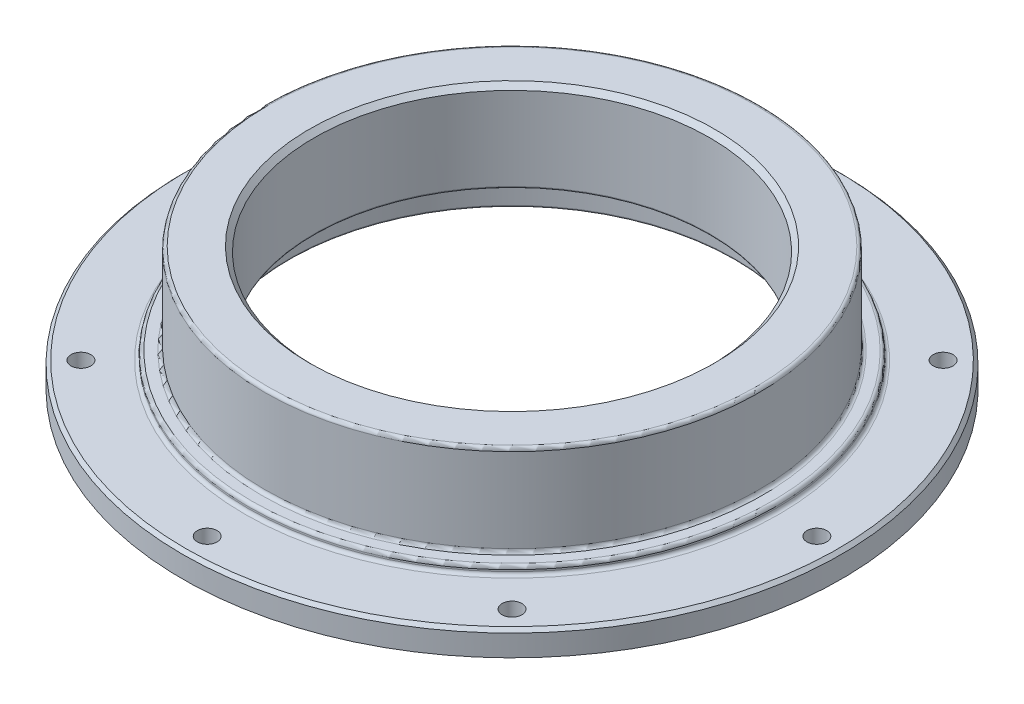
SolidWorks part; units mm, degrees
ref_plane "Front Plane" through (0, 0, 0) normal (0, 0, 1) x (1, 0, 0)
ref_plane "Top Plane" through (0, 0, 0) normal (0, 1, 0) x (1, 0, 0)
ref_plane "Right Plane" through (0, 0, 0) normal (1, 0, 0) x (0, 0, -1)
sketch "Sketch1" plane through (0, 0, 0) normal (0, 0, 1) x (1, 0, 0)
  line L0 (200, 0) -> (200, 15)
  line L1 (200, 15) -> (160, 15)
  line L2 (160, 15) -> (160, 20)
  line L3 (160, 20) -> (150, 20)
  line L4 (150, 20) -> (150, 75)
  line L5 (150, 75) -> (120, 75)
  line L6 (120, 75) -> (120, 0)
  line L7 (120, 0) -> (200, 0)
  line L8 (0, 0) -> (0, 134.8777) construction
  line L9 (120, 20.5) -> (135, 20.5)
  line L10 (135, 20.5) -> (135, 0)
  dimension "D1" = 200
  dimension "D2" = 75
  dimension "D3" = 5
  dimension "D4" = 15
  dimension "D5" = 120
  dimension "D6" = 30
  dimension "D7" = 10
  dimension "D8" = 15
  dimension "D9" = 20.5
revolve "Revolve1" add sketch "Sketch1" angle 360 about L8 region at (147.1445, 31.9866, 0)
ref_axis "Axis1" through (0, 75, 0) along (0, -1, 0)
sketch "Sketch2" plane through (0, 15, 0) normal (0, 1, 0) x (1, 0, 0)
  circle A0 centre (0, 0) radius 185 construction
  circle A1 centre (0, 185) radius 6
  dimension "D1" = 370
  dimension "D2" = 12
extrude "Cut-Extrude1" cut sketch "Sketch2" against normal through all
pattern_circular "CirPattern1" count 8 over 360 about axis through (0, 75, 0) along (0, -1, 0) of "Cut-Extrude1"
chamfer "Chamfer2" distance 3 angle 45 1 edges at (0, 75, -120)
fillet "Fillet1" radius 2 4 edges at (0, 20, -160) (0, 15, -160) (0, 20, -150) (0, 75, -150)
chamfer "Chamfer3" distance 2 angle 45 1 edges at (0, 15, -200)
fillet "Fillet2" radius 1 3 edges at (0, 20.5, -120) (0, 0, -135) (0, 20.5, -135)
